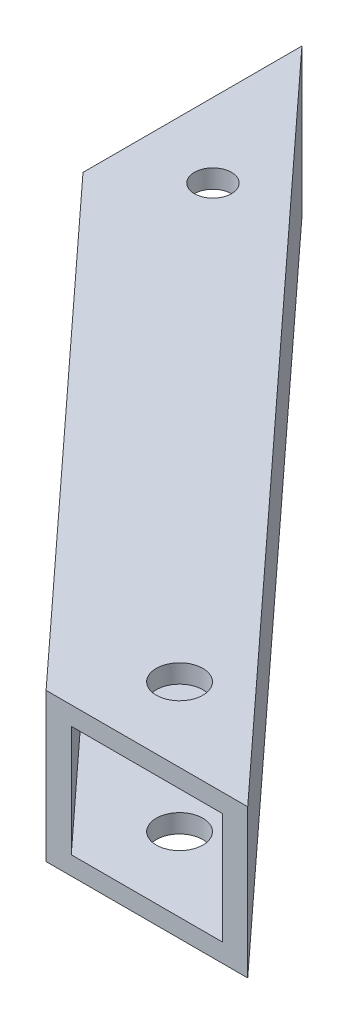
SolidWorks part; units mm, degrees
material "6061-T6 (SS)"
ref_plane "Front Plane" through (0, 0, 0) normal (0, 0, 1) x (1, 0, 0)
ref_plane "Top Plane" through (0, 0, 0) normal (0, 1, 0) x (1, 0, 0)
ref_plane "Right Plane" through (0, 0, 0) normal (1, 0, 0) x (0, 0, -1)
sketch "Sketch1" plane through (0, 0, 0) normal (0, 1, 0) x (1, 0, 0)
  line L0 (0, 0) -> (0, 117.475) construction
  line L1 (0, 0) -> (73.6599, 0) construction
  line L2 (108.1906, 0) -> (0, 117.475)
  line L3 (0, 117.475) -> (108.1906, 0)
  line L4 (0, 117.475) -> (-18.6836, 100.268)
  line L5 (108.1906, 0) -> (89.507, -17.207)
  line L6 (-18.6836, 100.268) -> (89.507, -17.207)
  line L7 (73.6599, 0) -> (108.1906, 0)
  dimension "D1" = 117.475
  dimension "D2" = 73.6599
  dimension "D3" = 25.4
extrude "Boss-Extrude3" add sketch "Sketch1" along normal blind 25.4 contours L4 L6 L5 L2 region at (41.1421, 0, -54.5491)
sketch "Sketch2" plane through (-58.5377, 0, -63.5637) normal (0.6774, 0, 0.7356) x (0.7356, 0, -0.6774)
  line L0 (54.1807, 25.4) -> (79.5807, 0) construction
  line L1 (79.5807, 0) -> (54.1807, 0) construction
  line L2 (57.3557, 3.175) -> (76.4057, 3.175)
  line L3 (57.3557, 3.175) -> (57.3557, 22.225)
  line L4 (57.3557, 22.225) -> (76.4057, 22.225)
  line L5 (76.4057, 3.175) -> (76.4057, 22.225)
  line L6 (57.3557, 3.175) -> (76.4057, 22.225) construction
  line L7 (57.3557, 22.225) -> (76.4057, 3.175) construction
  line L8 (79.5807, 25.4) -> (79.5807, 0) construction
  point P4 (66.8807, 12.7)
  dimension "D1" = 19.05
extrude "Cut-Extrude4" cut sketch "Sketch2" along normal up to surface (139.2362 mm away) up to face at (90.9252, 12.7, 0)
sketch "Sketch3" plane through (0, 25.4, 0) normal (0, 1, 0) x (1, 0, 0)
  line L0 (0, 117.475) -> (0, 79.981)
  line L1 (-18.6836, 100.268) -> (73.6599, 0) construction
  line L2 (0, 79.981) -> (-18.6836, 100.268)
  line L3 (-18.6836, 100.268) -> (0, 117.475)
  line L4 (108.1906, 0) -> (73.6599, 0)
  line L5 (73.6599, 0) -> (89.2506, -17.184)
  line L6 (89.2506, -17.184) -> (108.1906, 0)
  line L7 (-18.6836, 100.268) -> (73.6599, 0) construction
  line L8 (73.6599, 0) -> (108.1906, 0) construction
extrude "Cut-Extrude5" cut sketch "Sketch3" against normal blind 25.4
sketch "Sketch4" plane through (0, 25.4, 0) normal (0, 1, 0) x (1, 0, 0)
  line L0 (73.6599, 0) -> (73.6599, 37.494) construction
  line L1 (108.1906, 0) -> (0, 117.475) construction
  line L3 (73.6599, 0) -> (108.1906, 0) construction
  circle A0 centre (83.8199, 12.7) radius 3.9883
  dimension "D1" = 10.16
  dimension "D2" = 12.7
extrude "Cut-Extrude6" cut sketch "Sketch4" against normal blind 3.175
ref_plane "Plane1" through (0, 12.7, 0) normal (0, 1, 0) x (1, 0, 0)
mirror "Mirror1" about plane through (0, 12.7, 0) normal (0, 1, 0) of "Cut-Extrude6"
sketch "Sketch5" plane through (0, 0, 0) normal (0, -1, 0) x (1, 0, 0)
  line L0 (0, -79.981) -> (0, -117.475) construction
  circle A0 centre (12.7, -89.535) radius 3.175
  dimension "D1" = 6.35
  dimension "D2" = 12.7
  dimension "D3" = 27.94
extrude "Cut-Extrude7" cut sketch "Sketch5" against normal blind 3.175
mirror "Mirror2" about plane through (0, 12.7, 0) normal (0, 1, 0) of "Cut-Extrude7"
